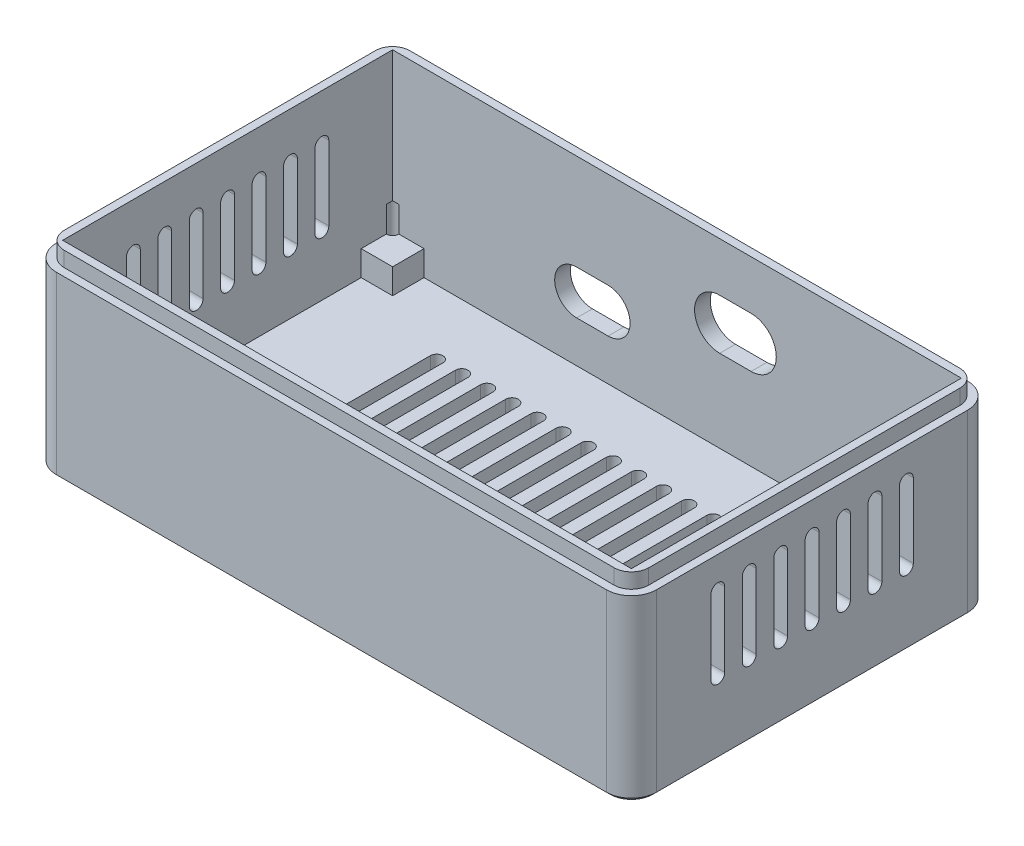
SolidWorks part; units mm, degrees
ref_plane "Front Plane" through (0, 0, 0) normal (0, 0, 1) x (1, 0, 0)
ref_plane "Top Plane" through (0, 0, 0) normal (0, 1, 0) x (1, 0, 0)
ref_plane "Right Plane" through (0, 0, 0) normal (1, 0, 0) x (0, 0, -1)
sketch "Croquis_contorno" plane through (0, 0, 0) normal (0, 1, 0) x (1, 0, 0)
  line L0 (-43.75, -28.75) -> (43.75, -28.75)
  line L1 (47.75, -24.75) -> (47.75, 24.75)
  line L2 (43.75, 28.75) -> (-43.75, 28.75)
  line L3 (-47.75, 24.75) -> (-47.75, -24.75)
  arc A0 (43.75, -28.75) -> (47.75, -24.75) centre (43.75, -24.75) ccw
  arc A1 (47.75, 24.75) -> (43.75, 28.75) centre (43.75, 24.75) ccw
  arc A2 (-43.75, 28.75) -> (-47.75, 24.75) centre (-43.75, 24.75) ccw
  arc A3 (-47.75, -24.75) -> (-43.75, -28.75) centre (-43.75, -24.75) ccw
  dimension "D3" = 4
  dimension "D1" = 95.5
  dimension "D2" = 57.5
extrude "Cuerpo" add sketch "Croquis_contorno" along normal blind 28.5
ref_plane "Plano_Top Plane_+28_5" through (0, 28.5, 0) normal (0, 1, 0) x (1, 0, 0)
sketch "Croquis_hueco_PCB" plane through (0, 28.5, 0) normal (0, 1, 0) x (1, 0, 0)
  line L1 (-45.25, -26.25) -> (45.25, -26.25)
  line L2 (-45.25, -26.25) -> (-45.25, 26.25)
  line L3 (-45.25, 26.25) -> (45.25, 26.25)
  line L4 (45.25, -26.25) -> (45.25, 26.25)
  line L5 (-45.25, -26.25) -> (45.25, 26.25) construction
  line L6 (-45.25, 26.25) -> (45.25, -26.25) construction
  dimension "D1" = 90.5
  dimension "D2" = 52.5
extrude "Hueco_PCB" cut sketch "Croquis_hueco_PCB" against normal blind 26.5
sketch "Croquis_labio" plane through (0, 28.5, 0) normal (0, 1, 0) x (1, 0, 0)
  line L0 (-43.75, -27.5) -> (43.75, -27.5)
  line L1 (46.5, -24.75) -> (46.5, 24.75)
  line L2 (43.75, 27.5) -> (-43.75, 27.5)
  line L3 (-46.5, 24.75) -> (-46.5, -24.75)
  line L5 (-45.25, -26.25) -> (45.25, -26.25)
  line L6 (-45.25, -26.25) -> (-45.25, 26.25)
  line L7 (-45.25, 26.25) -> (45.25, 26.25)
  line L8 (45.25, -26.25) -> (45.25, 26.25)
  line L9 (-45.25, -26.25) -> (45.25, 26.25) construction
  line L10 (-45.25, 26.25) -> (45.25, -26.25) construction
  arc A0 (43.75, -27.5) -> (46.5, -24.75) centre (43.75, -24.75) ccw
  arc A1 (46.5, 24.75) -> (43.75, 27.5) centre (43.75, 24.75) ccw
  arc A2 (-43.75, 27.5) -> (-46.5, 24.75) centre (-43.75, 24.75) ccw
  arc A3 (-46.5, -24.75) -> (-43.75, -27.5) centre (-43.75, -24.75) ccw
  point P12 (0, 0)
  dimension "D3" = 2.75
  dimension "D1" = 93
  dimension "D2" = 55
extrude "Labio_lip" add sketch "Croquis_labio" along normal blind 2.4
ref_plane "Plano_Top Plane_+2" through (0, 2, 0) normal (0, 1, 0) x (1, 0, 0)
sketch "Croquis_apoyos" plane through (0, 2, 0) normal (0, 1, 0) x (1, 0, 0)
  line L0 (45.25, 26.25) -> (-45.25, 26.25) construction
  line L1 (-45.25, -26.25) -> (-40.25, -26.25)
  line L2 (-45.25, -26.25) -> (-45.25, -21.25)
  line L3 (-45.25, -21.25) -> (-40.25, -21.25)
  line L4 (-40.25, -26.25) -> (-40.25, -21.25)
  line L5 (-45.25, -26.25) -> (-40.25, -21.25) construction
  line L6 (-45.25, -21.25) -> (-40.25, -26.25) construction
  line L7 (-45.25, 21.25) -> (-40.25, 21.25)
  line L8 (-45.25, 21.25) -> (-45.25, 26.25)
  line L9 (-45.25, 26.25) -> (-40.25, 26.25)
  line L10 (-40.25, 21.25) -> (-40.25, 26.25)
  line L11 (-45.25, 21.25) -> (-40.25, 26.25) construction
  line L12 (-45.25, 26.25) -> (-40.25, 21.25) construction
  line L13 (45.25, -26.25) -> (45.25, 26.25) construction
  line L14 (40.25, -26.25) -> (45.25, -26.25)
  line L15 (40.25, -26.25) -> (40.25, -21.25)
  line L16 (40.25, -21.25) -> (45.25, -21.25)
  line L17 (45.25, -26.25) -> (45.25, -21.25)
  line L18 (40.25, -26.25) -> (45.25, -21.25) construction
  line L19 (40.25, -21.25) -> (45.25, -26.25) construction
  line L21 (40.25, 21.25) -> (45.25, 21.25)
  line L22 (40.25, 21.25) -> (40.25, 26.25)
  line L23 (40.25, 26.25) -> (45.25, 26.25)
  line L24 (45.25, 21.25) -> (45.25, 26.25)
  line L25 (40.25, 21.25) -> (45.25, 26.25) construction
  line L26 (40.25, 26.25) -> (45.25, 21.25) construction
  point P0 (-42.75, 23.75)
  point P11 (42.75, -23.75)
  point P18 (42.75, 23.75)
  dimension "D1" = 5
  dimension "D2" = 5
extrude "Apoyos_PCB" add sketch "Croquis_apoyos" along normal blind 4
sketch "Croquis_alivios" plane through (0, 2, 0) normal (0, 1, 0) x (1, 0, 0)
  circle A0 centre (-45.25, -26.25) radius 1
  circle A1 centre (-45.25, 26.25) radius 1
  circle A2 centre (45.25, -26.25) radius 1
  circle A3 centre (45.25, 26.25) radius 1
  dimension "D1" = 2
extrude "Alivios_esquinas" cut sketch "Croquis_alivios" along normal blind 8.1
sketch "Croquis_salidas" plane through (0, 0, 0) normal (0, 0, 1) x (1, 0, 0)
  line L0 (6.8, 19.1) -> (11.8, 19.1) construction
  line L1 (6.8, 23.1) -> (11.8, 23.1)
  line L2 (6.8, 15.1) -> (11.8, 15.1)
  line L3 (-15.96, 12.1) -> (-10.96, 12.1) construction
  line L4 (-15.96, 15.6) -> (-10.96, 15.6)
  line L5 (-15.96, 8.6) -> (-10.96, 8.6)
  arc A0 (6.8, 23.1) -> (6.8, 15.1) centre (6.8, 19.1) ccw
  arc A1 (11.8, 15.1) -> (11.8, 23.1) centre (11.8, 19.1) ccw
  arc A2 (-15.96, 15.6) -> (-15.96, 8.6) centre (-15.96, 12.1) ccw
  arc A3 (-10.96, 8.6) -> (-10.96, 15.6) centre (-10.96, 12.1) ccw
  point P2 (9.3, 19.1)
  point P7 (-13.46, 12.1)
  point P14 (0, 0)
extrude "Salidas_USB_y_panel" cut sketch "Croquis_salidas" against normal through all
sketch "Croquis_ventilas" plane through (0, 0, 0) normal (1, 0, 0) x (0, 0, -1)
  line L0 (-15, 11.7) -> (-15, 23.5) construction
  line L1 (-16.1, 11.7) -> (-16.1, 23.5)
  line L2 (-13.9, 11.7) -> (-13.9, 23.5)
  line L3 (-10, 11.7) -> (-10, 23.5) construction
  line L4 (-11.1, 11.7) -> (-11.1, 23.5)
  line L5 (-8.9, 11.7) -> (-8.9, 23.5)
  line L6 (-5, 11.7) -> (-5, 23.5) construction
  line L7 (-6.1, 11.7) -> (-6.1, 23.5)
  line L8 (-3.9, 11.7) -> (-3.9, 23.5)
  line L9 (0, 11.7) -> (0, 23.5) construction
  line L10 (-1.1, 11.7) -> (-1.1, 23.5)
  line L11 (1.1, 11.7) -> (1.1, 23.5)
  line L12 (5, 11.7) -> (5, 23.5) construction
  line L13 (3.9, 11.7) -> (3.9, 23.5)
  line L14 (6.1, 11.7) -> (6.1, 23.5)
  line L15 (10, 11.7) -> (10, 23.5) construction
  line L16 (8.9, 11.7) -> (8.9, 23.5)
  line L17 (11.1, 11.7) -> (11.1, 23.5)
  line L18 (15, 11.7) -> (15, 23.5) construction
  line L19 (13.9, 11.7) -> (13.9, 23.5)
  line L20 (16.1, 11.7) -> (16.1, 23.5)
  arc A0 (-16.1, 11.7) -> (-13.9, 11.7) centre (-15, 11.7) ccw
  arc A1 (-13.9, 23.5) -> (-16.1, 23.5) centre (-15, 23.5) ccw
  arc A2 (-11.1, 11.7) -> (-8.9, 11.7) centre (-10, 11.7) ccw
  arc A3 (-8.9, 23.5) -> (-11.1, 23.5) centre (-10, 23.5) ccw
  arc A4 (-6.1, 11.7) -> (-3.9, 11.7) centre (-5, 11.7) ccw
  arc A5 (-3.9, 23.5) -> (-6.1, 23.5) centre (-5, 23.5) ccw
  arc A6 (-1.1, 11.7) -> (1.1, 11.7) centre (0, 11.7) ccw
  arc A7 (1.1, 23.5) -> (-1.1, 23.5) centre (0, 23.5) ccw
  arc A8 (3.9, 11.7) -> (6.1, 11.7) centre (5, 11.7) ccw
  arc A9 (6.1, 23.5) -> (3.9, 23.5) centre (5, 23.5) ccw
  arc A10 (8.9, 11.7) -> (11.1, 11.7) centre (10, 11.7) ccw
  arc A11 (11.1, 23.5) -> (8.9, 23.5) centre (10, 23.5) ccw
  arc A12 (13.9, 11.7) -> (16.1, 11.7) centre (15, 11.7) ccw
  arc A13 (16.1, 23.5) -> (13.9, 23.5) centre (15, 23.5) ccw
  point P2 (-15, 17.6)
  point P7 (-10, 17.6)
  point P14 (-5, 17.6)
  point P21 (0, 17.6)
  point P29 (5, 17.6)
  point P36 (10, 17.6)
  point P43 (15, 17.6)
  point P50 (0, 0)
extrude "Ventilas_laterales" cut sketch "Croquis_ventilas" along normal through all and the other way through all
sketch "Croquis_rejilla_piso" plane through (0, 0, 0) normal (0, 1, 0) x (1, 0, 0)
  line L0 (-28, -16) -> (-28, 16) construction
  line L1 (-29, -16) -> (-29, 16)
  line L2 (-27, -16) -> (-27, 16)
  line L3 (-24, -16) -> (-24, 16) construction
  line L4 (-25, -16) -> (-25, 16)
  line L5 (-23, -16) -> (-23, 16)
  line L6 (-20, -16) -> (-20, 16) construction
  line L7 (-21, -16) -> (-21, 16)
  line L8 (-19, -16) -> (-19, 16)
  line L9 (-16, -16) -> (-16, 16) construction
  line L10 (-17, -16) -> (-17, 16)
  line L11 (-15, -16) -> (-15, 16)
  line L12 (-12, -16) -> (-12, 16) construction
  line L13 (-13, -16) -> (-13, 16)
  line L14 (-11, -16) -> (-11, 16)
  line L15 (-8, -16) -> (-8, 16) construction
  line L16 (-9, -16) -> (-9, 16)
  line L17 (-7, -16) -> (-7, 16)
  line L18 (-4, -16) -> (-4, 16) construction
  line L19 (-5, -16) -> (-5, 16)
  line L20 (-3, -16) -> (-3, 16)
  line L21 (0, -16) -> (0, 16) construction
  line L22 (-1, -16) -> (-1, 16)
  line L23 (1, -16) -> (1, 16)
  line L24 (4, -16) -> (4, 16) construction
  line L25 (3, -16) -> (3, 16)
  line L26 (5, -16) -> (5, 16)
  line L27 (8, -16) -> (8, 16) construction
  line L28 (7, -16) -> (7, 16)
  line L29 (9, -16) -> (9, 16)
  line L30 (12, -16) -> (12, 16) construction
  line L31 (11, -16) -> (11, 16)
  line L32 (13, -16) -> (13, 16)
  line L33 (16, -16) -> (16, 16) construction
  line L34 (15, -16) -> (15, 16)
  line L35 (17, -16) -> (17, 16)
  line L36 (20, -16) -> (20, 16) construction
  line L37 (19, -16) -> (19, 16)
  line L38 (21, -16) -> (21, 16)
  line L39 (24, -16) -> (24, 16) construction
  line L40 (23, -16) -> (23, 16)
  line L41 (25, -16) -> (25, 16)
  line L42 (28, -16) -> (28, 16) construction
  line L43 (27, -16) -> (27, 16)
  line L44 (29, -16) -> (29, 16)
  arc A0 (-29, -16) -> (-27, -16) centre (-28, -16) ccw
  arc A1 (-27, 16) -> (-29, 16) centre (-28, 16) ccw
  arc A2 (-25, -16) -> (-23, -16) centre (-24, -16) ccw
  arc A3 (-23, 16) -> (-25, 16) centre (-24, 16) ccw
  arc A4 (-21, -16) -> (-19, -16) centre (-20, -16) ccw
  arc A5 (-19, 16) -> (-21, 16) centre (-20, 16) ccw
  arc A6 (-17, -16) -> (-15, -16) centre (-16, -16) ccw
  arc A7 (-15, 16) -> (-17, 16) centre (-16, 16) ccw
  arc A8 (-13, -16) -> (-11, -16) centre (-12, -16) ccw
  arc A9 (-11, 16) -> (-13, 16) centre (-12, 16) ccw
  arc A10 (-9, -16) -> (-7, -16) centre (-8, -16) ccw
  arc A11 (-7, 16) -> (-9, 16) centre (-8, 16) ccw
  arc A12 (-5, -16) -> (-3, -16) centre (-4, -16) ccw
  arc A13 (-3, 16) -> (-5, 16) centre (-4, 16) ccw
  arc A14 (-1, -16) -> (1, -16) centre (0, -16) ccw
  arc A15 (1, 16) -> (-1, 16) centre (0, 16) ccw
  arc A16 (3, -16) -> (5, -16) centre (4, -16) ccw
  arc A17 (5, 16) -> (3, 16) centre (4, 16) ccw
  arc A18 (7, -16) -> (9, -16) centre (8, -16) ccw
  arc A19 (9, 16) -> (7, 16) centre (8, 16) ccw
  arc A20 (11, -16) -> (13, -16) centre (12, -16) ccw
  arc A21 (13, 16) -> (11, 16) centre (12, 16) ccw
  arc A22 (15, -16) -> (17, -16) centre (16, -16) ccw
  arc A23 (17, 16) -> (15, 16) centre (16, 16) ccw
  arc A24 (19, -16) -> (21, -16) centre (20, -16) ccw
  arc A25 (21, 16) -> (19, 16) centre (20, 16) ccw
  arc A26 (23, -16) -> (25, -16) centre (24, -16) ccw
  arc A27 (25, 16) -> (23, 16) centre (24, 16) ccw
  arc A28 (27, -16) -> (29, -16) centre (28, -16) ccw
  arc A29 (29, 16) -> (27, 16) centre (28, 16) ccw
  point P2 (-28, 0)
  point P7 (-24, 0)
  point P14 (-20, 0)
  point P21 (-16, 0)
  point P28 (-12, 0)
  point P35 (-8, 0)
  point P42 (-4, 0)
  point P49 (0, 0)
  point P57 (4, 0)
  point P64 (8, 0)
  point P71 (12, 0)
  point P78 (16, 0)
  point P85 (20, 0)
  point P92 (24, 0)
  point P99 (28, 0)
  point P106 (0, 0)
extrude "Rejilla_piso" cut sketch "Croquis_rejilla_piso" along normal blind 2
chamfer "Chaflan_base" distance 0.6 angle 45 8 edges at (0, 0, 28.75) (46.5784, 0, 27.5784) (47.75, 0, 0) (46.5784, 0, -27.5784) (0, 0, -28.75) (-46.5784, 0, -27.5784) (-47.75, 0, 0) (-46.5784, 0, 27.5784) tangent propagation no
